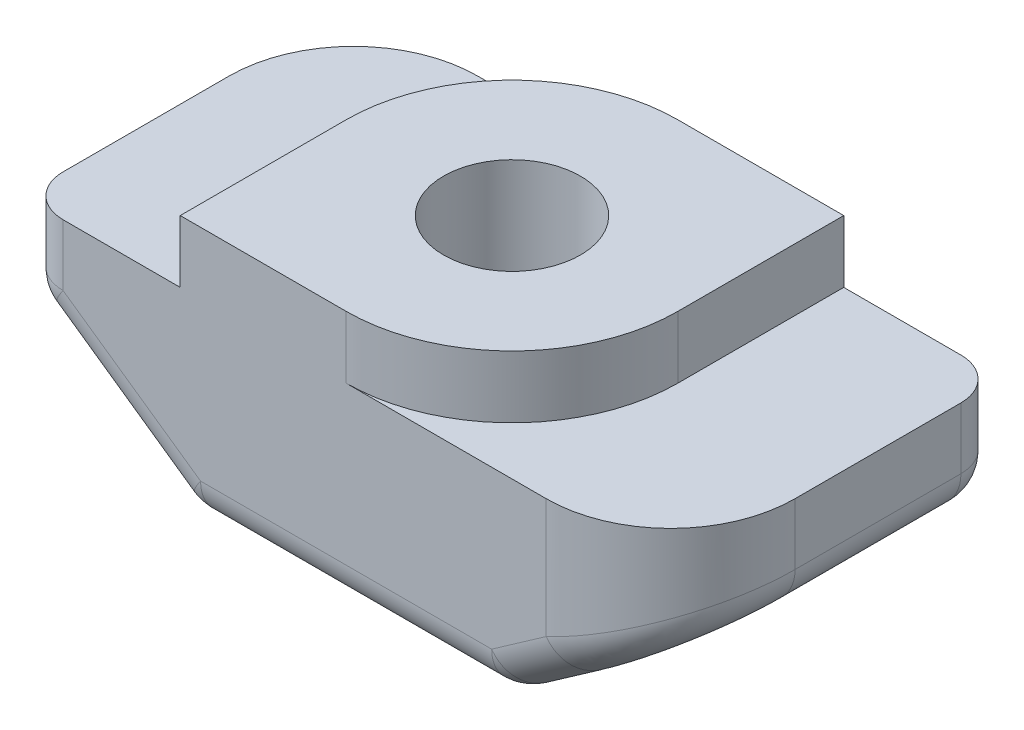
SolidWorks part; units mm, degrees
ref_plane "前基準面" through (0, 0, 0) normal (0, 0, 1) x (1, 0, 0)
ref_plane "上基準面" through (0, 0, 0) normal (0, 1, 0) x (1, 0, 0)
ref_plane "右基準面" through (0, 0, 0) normal (1, 0, 0) x (0, 0, -1)
sketch "草圖1" plane through (0, 0, 0) normal (0, 0, 1) x (1, 0, 0)
  line L0 (-7.825, -1.5) -> (-4, -1.5)
  line L1 (0, 0) -> (0, -6.3) construction
  line L2 (-4, -1.5) -> (-4, 0)
  line L3 (-4, 0) -> (4, 0)
  line L4 (4, 0) -> (4, -1.5)
  line L5 (-7.825, -1.5) -> (-7.825, -3.5)
  line L6 (-3.825, -6.3) -> (3.825, -6.3)
  line L7 (7.825, -1.5) -> (7.825, -3.5)
  line L8 (4, -1.5) -> (7.825, -1.5)
  line L11 (-3.825, -6.3) -> (-7.825, -3.5)
  line L12 (7.825, -3.5) -> (3.825, -6.3)
  dimension "D1" = 15.65
  dimension "D2" = 6.3
  dimension "D3" = 1.5
  dimension "D4" = 8
  dimension "D5" = 2
  dimension "D6" = 4
extrude "填料-伸長1" add sketch "草圖1" along normal mid plane 8
sketch "草圖2" plane through (0, 0, 0) normal (0, 1, 0) x (1, 0, 0)
  circle A0 centre (0, 0) radius 1.65
  dimension "D1" = 3.3
extrude "除料-伸長1" cut sketch "草圖2" against normal through all
cosmetic thread "鑽孔螺紋1" parameters "D1"=6.3, "D2"=4
hole_wizard "M4 螺紋孔1" positions "3D草圖1" profile "草圖3" tap size "M4" standard "Iso"
sketch3d "3D草圖1"
  point P0 (0, 0, 0)
sketch "草圖3" plane through (0, 0, 0) normal (1, 0, 0) x (0, 0, 1)
  line L0 (0, 0) -> (0, 12.4914)
  line L1 (0, 12.4914) -> (1.65, 11.5)
  line L2 (1.65, 11.5) -> (1.65, 0)
  line L5 (1.65, 0) -> (0, 0)
  line L10 (0, 12.4914) -> (-1.65, 11.5) construction
  line L11 (0, -6.35) -> (0, 107.95) construction
  dimension "螺孔鑽直徑" = 3.3
  dimension "螺孔鑽深度" = 11.5
  dimension "導頭角度" = 118
sketch "草圖4" plane through (0, 0, 0) normal (0, 1, 0) x (1, 0, 0)
  line L0 (-4, 0) -> (-4, -4)
  line L1 (-4, -4) -> (0, -4)
  line L2 (0, 4) -> (4, 4)
  line L3 (4, 4) -> (4, 0)
  arc A0 (0, -4) -> (4, 0) centre (0, 0) ccw
  arc A1 (0, 4) -> (-4, 0) centre (0, 0) ccw
extrude "除料-伸長2" cut sketch "草圖4" against normal blind 1.5 flip side to cut
fillet "圓角1" radius 3 2 edges at (-7.825, -2.5, -4) (7.825, -2.5, 4)
fillet "圓角2" radius 1 2 edges at (-7.825, -2.5, 4) (7.825, -2.5, -4)
fillet "圓角3" radius 1 14 edges at (4.325, -5.95, 4) (6.9463, -4.1151, 3.1213) (7.825, -3.5, -1) (7.5321, -3.705, -3.7071) (-4.325, -5.95, -4) (-6.9463, -4.1151, -3.1213) (-7.825, -3.5, 1) (-7.5321, -3.705, 3.7071) (5.325, -5.25, -4) (3.825, -6.3, 0) (0, -6.3, -4) (-5.325, -5.25, 4) (-3.825, -6.3, 0) (0, -6.3, 4)
